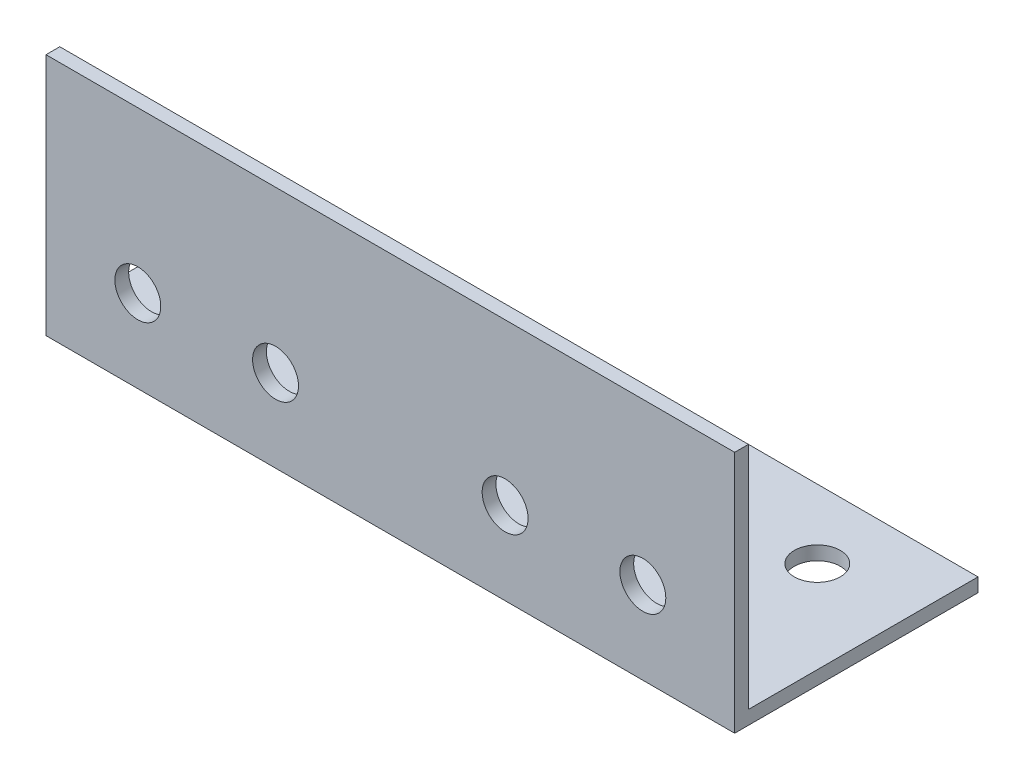
SolidWorks part; units mm, degrees
ref_plane "Спереди" through (0, 0, 0) normal (0, 0, 1) x (1, 0, 0)
ref_plane "Сверху" through (0, 0, 0) normal (0, 1, 0) x (1, 0, 0)
ref_plane "Справа" through (0, 0, 0) normal (1, 0, 0) x (0, 0, -1)
sketch "Эскиз1" plane through (0, 0, 0) normal (1, 0, 0) x (0, 0, -1)
  line L0 (0, 0) -> (0, 50)
  line L1 (0, 0) -> (50, 0)
extrude "Вытянуть-Тонкостенный1" add sketch "Эскиз1" along normal blind 150 thin thin type one direction wall 3
sketch "Эскиз2" plane through (0, -3, 0) normal (0, -1, 0) x (1, 0, 0)
  line L0 (75, -58.7293) -> (75, -21.2393) construction
  circle A0 centre (130, -35) radius 5
  circle A1 centre (100, -35) radius 5
  circle A2 centre (50, -35) radius 5
  circle A3 centre (20, -35) radius 5
  dimension "D1" = 2
extrude "Вырез-Вытянуть1" cut sketch "Эскиз2" against normal through all
sketch "Эскиз3" plane through (0, 0, 3) normal (0, 0, 1) x (1, 0, 0)
  line L0 (75, 50) -> (75, 0) construction
  line L1 (150, 50) -> (0, 50) construction
  circle A0 centre (130, 15) radius 5
  circle A1 centre (100, 15) radius 5
  circle A2 centre (50, 15) radius 5
  circle A3 centre (20, 15) radius 5
  dimension "D1" = 2
extrude "Вырез-Вытянуть3" cut sketch "Эскиз3" against normal through all
